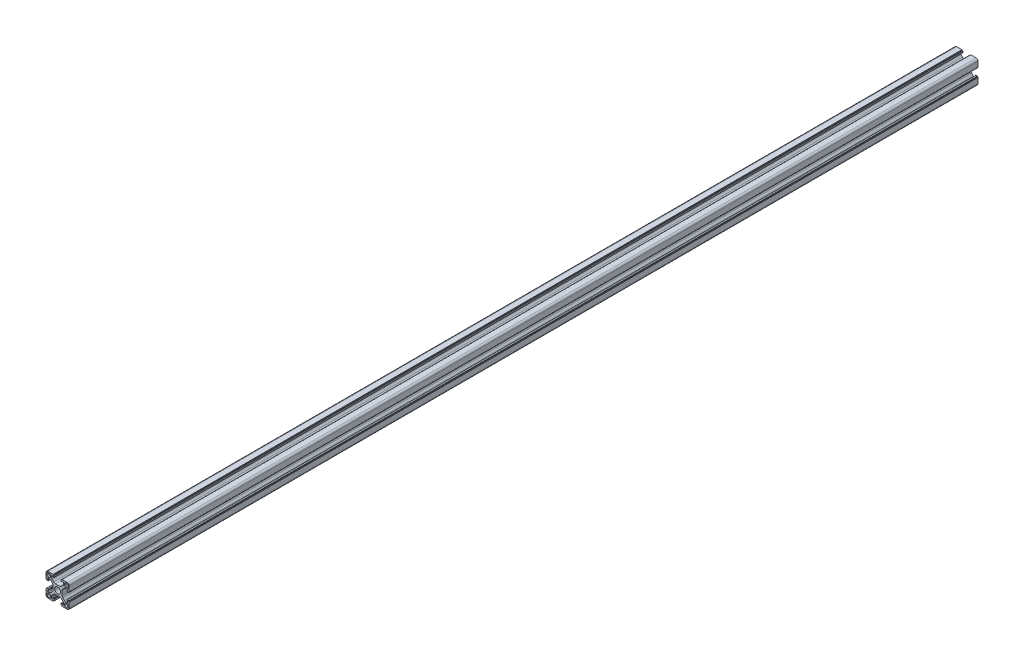
SolidWorks part; units mm, degrees
ref_plane "Спереди" through (0, 0, 0) normal (0, 0, 1) x (1, 0, 0)
ref_plane "Сверху" through (0, 0, 0) normal (0, 1, 0) x (1, 0, 0)
ref_plane "Справа" through (0, 0, 0) normal (1, 0, 0) x (0, 0, -1)
sketch "Эскиз2" plane through (0, 0, 0) normal (0, 0, 1) x (1, 0, 0)
  line L0 (9.2299, 9.7837) -> (6.2299, 6.7837) construction
  line L1 (0.1299, 4.6837) -> (2.0286, 4.6837)
  line L2 (0.1299, 0.6837) -> (10.1299, 10.6837) construction
  line L3 (7.7299, 8.2837) -> (6.2299, 9.7837) construction
  line L4 (3.4428, 5.2695) -> (4.7441, 6.5707)
  line L5 (7.0299, 6.7837) -> (8.4299, 6.7837)
  line L6 (6.2299, 7.5837) -> (6.2299, 8.9837)
  line L7 (8.4299, 9.7837) -> (7.0299, 9.7837)
  line L8 (5.3299, 8.8837) -> (5.3299, 7.9849)
  line L9 (3.8931, 8.757) -> (4.3734, 9.2373)
  line L10 (3.3299, 10.2328) -> (3.8299, 10.2328)
  line L11 (3.7163, 8.6837) -> (3.4299, 8.6837)
  line L12 (4.727, 9.3837) -> (4.8299, 9.3837)
  line L13 (3.8299, 10.5337) -> (3.8299, 10.2328)
  line L14 (3.1799, 10.0828) -> (3.1799, 8.9337)
  line L15 (8.6299, 10.6837) -> (3.9799, 10.6837)
  line L16 (9.2299, 8.9837) -> (9.2299, 7.5837)
  line L17 (10.1299, 9.1837) -> (10.1299, 4.5337)
  line L18 (9.5289, 3.7337) -> (8.3799, 3.7337)
  line L19 (9.9799, 4.3837) -> (9.6789, 4.3837)
  line L20 (8.8299, 5.2808) -> (8.8299, 5.3837)
  line L21 (8.1299, 4.2702) -> (8.1299, 3.9837)
  line L22 (9.6789, 3.8837) -> (9.6789, 4.3837)
  line L23 (8.2031, 4.447) -> (8.6834, 4.9273)
  line L24 (8.3299, 5.8837) -> (7.4311, 5.8837)
  line L25 (4.7156, 3.9967) -> (6.0169, 5.2979)
  line L26 (4.1299, 0.6837) -> (4.1299, 2.5825)
  line L27 (4.1299, 0.6837) -> (4.1299, -1.2151)
  line L28 (4.7156, -2.6293) -> (6.0169, -3.9305)
  line L29 (6.2299, -6.2163) -> (6.2299, -7.6163)
  line L30 (7.0299, -5.4163) -> (8.4299, -5.4163)
  line L31 (9.2299, -7.6163) -> (9.2299, -6.2163)
  line L32 (8.3299, -4.5163) -> (7.4311, -4.5163)
  line L33 (8.2031, -3.0795) -> (8.6834, -3.5598)
  line L34 (9.6789, -2.5163) -> (9.6789, -3.0163)
  line L35 (8.1299, -2.9027) -> (8.1299, -2.6163)
  line L36 (8.8299, -3.9134) -> (8.8299, -4.0163)
  line L37 (9.9799, -3.0163) -> (9.6789, -3.0163)
  line L38 (9.5289, -2.3663) -> (8.3799, -2.3663)
  line L39 (10.1299, -7.8163) -> (10.1299, -3.1663)
  line L40 (8.4299, -8.4163) -> (7.0299, -8.4163)
  line L41 (8.6299, -9.3163) -> (3.9799, -9.3163)
  line L42 (3.1799, -8.7153) -> (3.1799, -7.5663)
  line L43 (3.8299, -9.1663) -> (3.8299, -8.8653)
  line L44 (4.727, -8.0163) -> (4.8299, -8.0163)
  line L45 (3.7163, -7.3163) -> (3.4299, -7.3163)
  line L46 (3.3299, -8.8653) -> (3.8299, -8.8653)
  line L47 (3.8931, -7.3895) -> (4.3734, -7.8698)
  line L48 (5.3299, -7.5163) -> (5.3299, -6.6175)
  line L49 (3.4428, -3.9021) -> (4.7441, -5.2033)
  line L50 (0.1299, -3.3163) -> (2.0286, -3.3163)
  line L51 (9.2299, -8.4163) -> (6.2299, -5.4163) construction
  line L52 (0.1299, 0.6837) -> (10.1299, -9.3163) construction
  line L53 (7.7299, -6.9163) -> (9.2299, -5.4163) construction
  line L54 (0.1299, -3.3163) -> (-1.7689, -3.3163)
  line L55 (-3.1831, -3.9021) -> (-4.4844, -5.2033)
  line L56 (-6.7701, -5.4163) -> (-8.1701, -5.4163)
  line L57 (-5.9701, -6.2163) -> (-5.9701, -7.6163)
  line L58 (-8.1701, -8.4163) -> (-6.7701, -8.4163)
  line L59 (-5.0701, -7.5163) -> (-5.0701, -6.6175)
  line L60 (-3.6334, -7.3895) -> (-4.1137, -7.8698)
  line L61 (-3.0701, -8.8653) -> (-3.5701, -8.8653)
  line L62 (-3.4566, -7.3163) -> (-3.1701, -7.3163)
  line L63 (-4.4673, -8.0163) -> (-4.5701, -8.0163)
  line L64 (-3.5701, -9.1663) -> (-3.5701, -8.8653)
  line L65 (-2.9201, -8.7153) -> (-2.9201, -7.5663)
  line L66 (-8.3701, -9.3163) -> (-3.7201, -9.3163)
  line L67 (-8.9701, -7.6163) -> (-8.9701, -6.2163)
  line L68 (-9.8701, -7.8163) -> (-9.8701, -3.1663)
  line L69 (-9.2692, -2.3663) -> (-8.1201, -2.3663)
  line L70 (-9.7201, -3.0163) -> (-9.4192, -3.0163)
  line L71 (-8.5701, -3.9134) -> (-8.5701, -4.0163)
  line L72 (-7.8701, -2.9027) -> (-7.8701, -2.6163)
  line L73 (-9.4192, -2.5163) -> (-9.4192, -3.0163)
  line L74 (-7.9434, -3.0795) -> (-8.4237, -3.5598)
  line L75 (-8.0701, -4.5163) -> (-7.1714, -4.5163)
  line L76 (-4.4559, -2.6293) -> (-5.7572, -3.9305)
  line L77 (-3.8701, 0.6837) -> (-3.8701, -1.2151)
  line L78 (-8.9701, -8.4163) -> (-5.9701, -5.4163) construction
  line L79 (0.1299, 0.6837) -> (-9.8701, -9.3163) construction
  line L80 (-7.4701, -6.9163) -> (-5.9701, -8.4163) construction
  line L81 (-3.8701, 0.6837) -> (-3.8701, 2.5825)
  line L82 (-4.4559, 3.9967) -> (-5.7572, 5.2979)
  line L83 (-5.9701, 7.5837) -> (-5.9701, 8.9837)
  line L84 (-6.7701, 6.7837) -> (-8.1701, 6.7837)
  line L85 (-8.9701, 8.9837) -> (-8.9701, 7.5837)
  line L86 (-8.0701, 5.8837) -> (-7.1714, 5.8837)
  line L87 (-7.9434, 4.447) -> (-8.4237, 4.9273)
  line L88 (-9.4192, 3.8837) -> (-9.4192, 4.3837)
  line L89 (-7.8701, 4.2702) -> (-7.8701, 3.9837)
  line L90 (-8.5701, 5.2808) -> (-8.5701, 5.3837)
  line L91 (-9.7201, 4.3837) -> (-9.4192, 4.3837)
  line L92 (-9.2692, 3.7337) -> (-8.1201, 3.7337)
  line L93 (-9.8701, 9.1837) -> (-9.8701, 4.5337)
  line L94 (-8.1701, 9.7837) -> (-6.7701, 9.7837)
  line L95 (-8.3701, 10.6837) -> (-3.7201, 10.6837)
  line L96 (-2.9201, 10.0828) -> (-2.9201, 8.9337)
  line L97 (-3.5701, 10.5337) -> (-3.5701, 10.2328)
  line L98 (-4.4673, 9.3837) -> (-4.5701, 9.3837)
  line L99 (-3.4566, 8.6837) -> (-3.1701, 8.6837)
  line L100 (-3.0701, 10.2328) -> (-3.5701, 10.2328)
  line L101 (-3.6334, 8.757) -> (-4.1137, 9.2373)
  line L102 (-5.0701, 8.8837) -> (-5.0701, 7.9849)
  line L103 (-3.1831, 5.2695) -> (-4.4844, 6.5707)
  line L104 (0.1299, 4.6837) -> (-1.7689, 4.6837)
  line L105 (-11.6342, 0.6837) -> (11.6342, 0.6837) construction
  line L106 (-8.9701, 9.7837) -> (-5.9701, 6.7837) construction
  line L107 (0.1299, -11.4027) -> (0.1299, 11.4027) construction
  line L108 (0.1299, 0.6837) -> (-9.8701, 10.6837) construction
  line L109 (-7.4701, 8.2837) -> (-8.9701, 6.7837) construction
  arc A0 (9.2299, 8.9837) -> (8.4299, 9.7837) centre (8.4299, 8.9837) ccw
  arc A1 (7.0299, 9.7837) -> (6.2299, 8.9837) centre (7.0299, 8.9837) ccw
  arc A2 (7.0299, 6.7837) -> (6.2299, 7.5837) centre (7.0299, 7.5837) cw
  arc A3 (8.6299, 10.6837) -> (10.1299, 9.1837) centre (8.6299, 9.1837) cw
  arc A4 (3.3299, 10.2328) -> (3.1799, 10.0828) centre (3.3299, 10.0828) ccw
  arc A5 (3.9799, 10.6837) -> (3.8299, 10.5337) centre (3.9799, 10.5337) ccw
  arc A6 (3.7163, 8.6837) -> (3.8931, 8.757) centre (3.7163, 8.9337) ccw
  arc A7 (3.4299, 8.6837) -> (3.1799, 8.9337) centre (3.4299, 8.9337) cw
  arc A8 (4.3734, 9.2373) -> (4.727, 9.3837) centre (4.727, 8.8837) cw
  arc A9 (4.8299, 9.3837) -> (5.3299, 8.8837) centre (4.8299, 8.8837) cw
  arc A10 (2.6299, 0.6837) -> (0.1299, 3.1837) centre (0.1299, 0.6837) ccw
  arc A11 (2.0286, 4.6837) -> (3.4428, 5.2695) centre (2.0286, 6.6837) ccw
  arc A12 (5.3299, 7.9849) -> (4.7441, 6.5707) centre (3.3299, 7.9849) cw
  arc A13 (9.2299, 7.5837) -> (8.4299, 6.7837) centre (8.4299, 7.5837) cw
  arc A14 (8.8299, 5.3837) -> (8.3299, 5.8837) centre (8.3299, 5.3837) ccw
  arc A15 (8.6834, 4.9273) -> (8.8299, 5.2808) centre (8.3299, 5.2808) ccw
  arc A16 (8.1299, 3.9837) -> (8.3799, 3.7337) centre (8.3799, 3.9837) ccw
  arc A17 (8.1299, 4.2702) -> (8.2031, 4.447) centre (8.3799, 4.2702) cw
  arc A18 (10.1299, 4.5337) -> (9.9799, 4.3837) centre (9.9799, 4.5337) cw
  arc A19 (9.6789, 3.8837) -> (9.5289, 3.7337) centre (9.5289, 3.8837) cw
  arc A20 (7.4311, 5.8837) -> (6.0169, 5.2979) centre (7.4311, 3.8837) ccw
  arc A21 (4.1299, 2.5825) -> (4.7156, 3.9967) centre (6.1299, 2.5825) cw
  arc A22 (8.4299, -8.4163) -> (9.2299, -7.6163) centre (8.4299, -7.6163) ccw
  arc A23 (9.2299, -6.2163) -> (8.4299, -5.4163) centre (8.4299, -6.2163) ccw
  arc A24 (6.2299, -6.2163) -> (7.0299, -5.4163) centre (7.0299, -6.2163) cw
  arc A25 (10.1299, -7.8163) -> (8.6299, -9.3163) centre (8.6299, -7.8163) cw
  arc A26 (9.6789, -2.5163) -> (9.5289, -2.3663) centre (9.5289, -2.5163) ccw
  arc A27 (10.1299, -3.1663) -> (9.9799, -3.0163) centre (9.9799, -3.1663) ccw
  arc A28 (8.1299, -2.9027) -> (8.2031, -3.0795) centre (8.3799, -2.9027) ccw
  arc A29 (8.1299, -2.6163) -> (8.3799, -2.3663) centre (8.3799, -2.6163) cw
  arc A30 (8.6834, -3.5598) -> (8.8299, -3.9134) centre (8.3299, -3.9134) cw
  arc A31 (8.8299, -4.0163) -> (8.3299, -4.5163) centre (8.3299, -4.0163) cw
  arc A32 (0.1299, -1.8163) -> (2.6299, 0.6837) centre (0.1299, 0.6837) ccw
  arc A33 (4.1299, -1.2151) -> (4.7156, -2.6293) centre (6.1299, -1.2151) ccw
  arc A34 (7.4311, -4.5163) -> (6.0169, -3.9305) centre (7.4311, -2.5163) cw
  arc A35 (7.0299, -8.4163) -> (6.2299, -7.6163) centre (7.0299, -7.6163) cw
  arc A36 (4.8299, -8.0163) -> (5.3299, -7.5163) centre (4.8299, -7.5163) ccw
  arc A37 (4.3734, -7.8698) -> (4.727, -8.0163) centre (4.727, -7.5163) ccw
  arc A38 (3.4299, -7.3163) -> (3.1799, -7.5663) centre (3.4299, -7.5663) ccw
  arc A39 (3.7163, -7.3163) -> (3.8931, -7.3895) centre (3.7163, -7.5663) cw
  arc A40 (3.9799, -9.3163) -> (3.8299, -9.1663) centre (3.9799, -9.1663) cw
  arc A41 (3.3299, -8.8653) -> (3.1799, -8.7153) centre (3.3299, -8.7153) cw
  arc A42 (5.3299, -6.6175) -> (4.7441, -5.2033) centre (3.3299, -6.6175) ccw
  arc A43 (2.0286, -3.3163) -> (3.4428, -3.9021) centre (2.0286, -5.3163) cw
  arc A44 (-8.9701, -7.6163) -> (-8.1701, -8.4163) centre (-8.1701, -7.6163) ccw
  arc A45 (-6.7701, -8.4163) -> (-5.9701, -7.6163) centre (-6.7701, -7.6163) ccw
  arc A46 (-6.7701, -5.4163) -> (-5.9701, -6.2163) centre (-6.7701, -6.2163) cw
  arc A47 (-8.3701, -9.3163) -> (-9.8701, -7.8163) centre (-8.3701, -7.8163) cw
  arc A48 (-3.0701, -8.8653) -> (-2.9201, -8.7153) centre (-3.0701, -8.7153) ccw
  arc A49 (-3.7201, -9.3163) -> (-3.5701, -9.1663) centre (-3.7201, -9.1663) ccw
  arc A50 (-3.4566, -7.3163) -> (-3.6334, -7.3895) centre (-3.4566, -7.5663) ccw
  arc A51 (-3.1701, -7.3163) -> (-2.9201, -7.5663) centre (-3.1701, -7.5663) cw
  arc A52 (-4.1137, -7.8698) -> (-4.4673, -8.0163) centre (-4.4673, -7.5163) cw
  arc A53 (-4.5701, -8.0163) -> (-5.0701, -7.5163) centre (-4.5701, -7.5163) cw
  arc A54 (-2.3701, 0.6837) -> (0.1299, -1.8163) centre (0.1299, 0.6837) ccw
  arc A55 (-1.7689, -3.3163) -> (-3.1831, -3.9021) centre (-1.7689, -5.3163) ccw
  arc A56 (-5.0701, -6.6175) -> (-4.4844, -5.2033) centre (-3.0701, -6.6175) cw
  arc A57 (-8.9701, -6.2163) -> (-8.1701, -5.4163) centre (-8.1701, -6.2163) cw
  arc A58 (-8.5701, -4.0163) -> (-8.0701, -4.5163) centre (-8.0701, -4.0163) ccw
  arc A59 (-8.4237, -3.5598) -> (-8.5701, -3.9134) centre (-8.0701, -3.9134) ccw
  arc A60 (-7.8701, -2.6163) -> (-8.1201, -2.3663) centre (-8.1201, -2.6163) ccw
  arc A61 (-7.8701, -2.9027) -> (-7.9434, -3.0795) centre (-8.1201, -2.9027) cw
  arc A62 (-9.8701, -3.1663) -> (-9.7201, -3.0163) centre (-9.7201, -3.1663) cw
  arc A63 (-9.4192, -2.5163) -> (-9.2692, -2.3663) centre (-9.2692, -2.5163) cw
  arc A64 (-7.1714, -4.5163) -> (-5.7572, -3.9305) centre (-7.1714, -2.5163) ccw
  arc A65 (-3.8701, -1.2151) -> (-4.4559, -2.6293) centre (-5.8701, -1.2151) cw
  arc A66 (-8.1701, 9.7837) -> (-8.9701, 8.9837) centre (-8.1701, 8.9837) ccw
  arc A67 (-8.9701, 7.5837) -> (-8.1701, 6.7837) centre (-8.1701, 7.5837) ccw
  arc A68 (-5.9701, 7.5837) -> (-6.7701, 6.7837) centre (-6.7701, 7.5837) cw
  arc A69 (-9.8701, 9.1837) -> (-8.3701, 10.6837) centre (-8.3701, 9.1837) cw
  arc A70 (-9.4192, 3.8837) -> (-9.2692, 3.7337) centre (-9.2692, 3.8837) ccw
  arc A71 (-9.8701, 4.5337) -> (-9.7201, 4.3837) centre (-9.7201, 4.5337) ccw
  arc A72 (-7.8701, 4.2702) -> (-7.9434, 4.447) centre (-8.1201, 4.2702) ccw
  arc A73 (-7.8701, 3.9837) -> (-8.1201, 3.7337) centre (-8.1201, 3.9837) cw
  arc A74 (-8.4237, 4.9273) -> (-8.5701, 5.2808) centre (-8.0701, 5.2808) cw
  arc A75 (-8.5701, 5.3837) -> (-8.0701, 5.8837) centre (-8.0701, 5.3837) cw
  arc A76 (0.1299, 3.1837) -> (-2.3701, 0.6837) centre (0.1299, 0.6837) ccw
  arc A77 (-3.8701, 2.5825) -> (-4.4559, 3.9967) centre (-5.8701, 2.5825) ccw
  arc A78 (-7.1714, 5.8837) -> (-5.7572, 5.2979) centre (-7.1714, 3.8837) cw
  arc A79 (-6.7701, 9.7837) -> (-5.9701, 8.9837) centre (-6.7701, 8.9837) cw
  arc A80 (-4.5701, 9.3837) -> (-5.0701, 8.8837) centre (-4.5701, 8.8837) ccw
  arc A81 (-4.1137, 9.2373) -> (-4.4673, 9.3837) centre (-4.4673, 8.8837) ccw
  arc A82 (-3.1701, 8.6837) -> (-2.9201, 8.9337) centre (-3.1701, 8.9337) ccw
  arc A83 (-3.4566, 8.6837) -> (-3.6334, 8.757) centre (-3.4566, 8.9337) cw
  arc A84 (-3.7201, 10.6837) -> (-3.5701, 10.5337) centre (-3.7201, 10.5337) cw
  arc A85 (-3.0701, 10.2328) -> (-2.9201, 10.0828) centre (-3.0701, 10.0828) cw
  arc A86 (-5.0701, 7.9849) -> (-4.4844, 6.5707) centre (-3.0701, 7.9849) ccw
  arc A87 (-1.7689, 4.6837) -> (-3.1831, 5.2695) centre (-1.7689, 6.6837) cw
  point P0 (0.1299, 0.6837)
  point P9 (0.1299, 0.6837)
  point P40 (8.8299, 4.3837)
  point P93 (3.8299, -8.0163)
  point P144 (3.8299, 9.3837)
  point P152 (8.8299, -3.0163)
  point P153 (0.1299, -3.2405)
  point P154 (0.1299, 0.6837)
  point P189 (-8.5701, -3.0163)
  point P228 (-3.5701, -8.0163)
  point P229 (-3.7944, 0.6837)
  point P230 (0.1299, 0.6837)
  point P268 (-3.5701, 9.3837)
  point P273 (4.0541, 0.6837)
  point P306 (-8.5701, 4.3837)
  point P307 (0.1299, 4.608)
  point P309 (0.1299, 0.6837)
  dimension "D3" = 5
  dimension "D6" = 2
  dimension "D1" = 2
  dimension "D2" = 6
  dimension "D4" = 4
  dimension "D5" = 0.9
extrude "Бобышка-Вытянуть1" add sketch "Эскиз2" along normal blind 784
